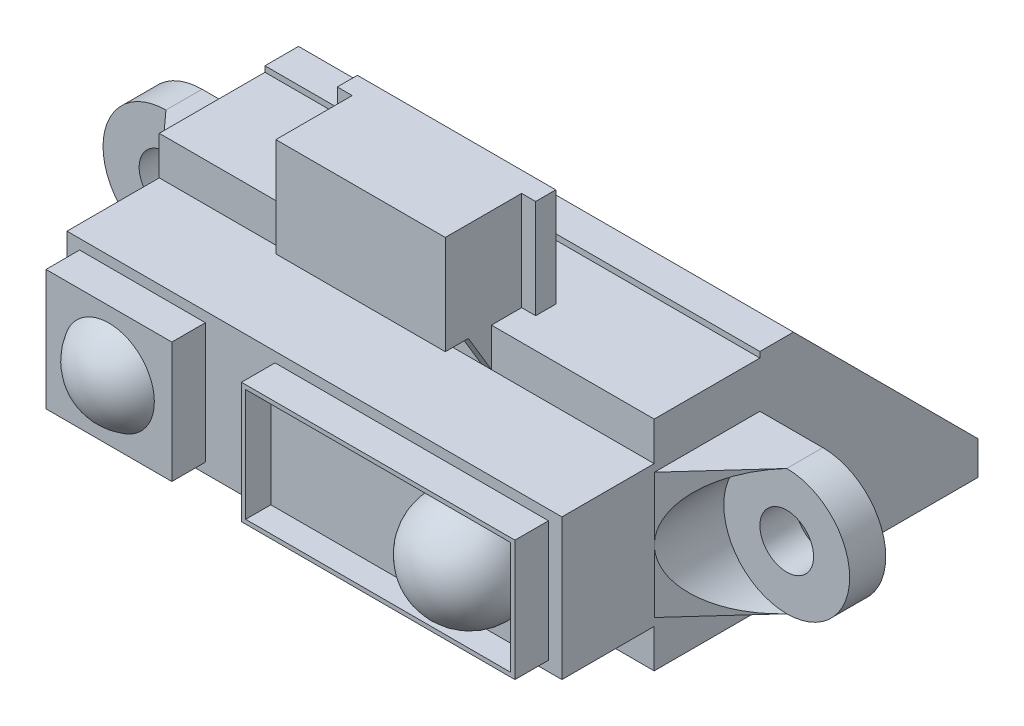
SolidWorks part; units mm, degrees
ref_plane "Plan de face" through (0, 0, 0) normal (0, 0, 1) x (1, 0, 0)
ref_plane "Plan de dessus" through (0, 0, 0) normal (0, 1, 0) x (1, 0, 0)
ref_plane "Plan de droite" through (0, 0, 0) normal (1, 0, 0) x (0, 0, -1)
sketch "Esquisse1" plane through (0, 0, 0) normal (0, 0, 1) x (1, 0, 0)
  line L1 (1.5656, 3.4963) -> (16.3156, 3.4963)
  line L3 (1.5656, -9.5037) -> (16.3156, -9.5037)
  line L4 (16.3156, 3.4963) -> (16.3156, -9.5037)
  line L7 (20.0656, -7.0914) -> (16.3156, -7.0914)
  line L8 (20.0656, 0.4086) -> (16.3156, 0.4086)
  line L9 (16.3156, 0.4086) -> (16.3156, -7.0914)
  line L10 (1.5656, 3.4963) -> (1.5656, -9.5037)
  arc A1 (20.0656, -7.0914) -> (20.0656, 0.4086) centre (20.0656, -3.3414) ccw
  circle A3 centre (20.0656, -3.3414) radius 1.6
  dimension "D5" = 7.5
  dimension "D6" = 3.2
  dimension "D1" = 14.75
  dimension "D2" = 13
extrude "Boss.-Extru.2" add sketch "Esquisse1" along normal blind 2.15 contours A1 L8 L9 L7
sketch "Esquisse2" plane through (0, 0, 0) normal (0, 0, 1) x (1, 0, 0)
  line L0 (16.3156, 0.4086) -> (16.3156, -7.0914) construction
  line L1 (1.5656, 3.1586) -> (16.3156, 3.1586)
  line L2 (1.5656, 3.1586) -> (1.5656, -9.8414)
  line L3 (1.5656, -9.8414) -> (16.3156, -9.8414)
  line L4 (16.3156, 3.1586) -> (16.3156, -9.8414)
  dimension "D3" = 0
  dimension "D1" = 14.75
  dimension "D2" = 13
  dimension "D4" = 2.75
extrude "Boss.-Extru.3" add sketch "Esquisse2" along normal blind 6.3 separate body
sketch "Esquisse8" plane through (16.3156, 0, 0) normal (1, 0, 0) x (0, 0, -1)
  line L0 (-2.1441, -7.0745) -> (-6.3, -7.0745)
  line L1 (-6.3, -9.8414) -> (-6.3, 3.1586) construction
  line L2 (-2.1441, 0.4088) -> (-6.3, 0.4088)
  line L3 (-6.3, -7.0745) -> (-6.3, 0.4088)
  line L4 (-2.1441, 0.4088) -> (-2.1441, -7.0745)
sketch "Esquisse9" plane through (0, 0, 2.15) normal (0, 0, 1) x (1, 0, 0)
  line L0 (20.0656, -7.0914) -> (16.3156, -7.0914) construction
  line L1 (16.3156, 0.4086) -> (19.8581, 0.4086)
  line L2 (16.3156, 0.4086) -> (16.3156, -7.0914)
  line L3 (16.3156, -7.0914) -> (19.8581, -7.0914)
  line L4 (19.8581, 0.4086) -> (19.8581, -7.0914)
sketch "Esquisse10" plane through (0, -7.0914, 0) normal (0, -1, 0) x (1, 0, 0)
  line L0 (16.3156, 6.2878) -> (20.0656, 2.15)
  line L1 (16.3156, 2.1441) -> (16.3156, 6.3) construction
  line L2 (20.0656, 2.15) -> (16.3156, 2.15)
  line L3 (16.3156, 2.15) -> (19.8581, 2.15) construction
  line L4 (16.3156, 2.15) -> (16.3156, 6.2878)
extrude "Boss.-Extru.4" add sketch "Esquisse10" against normal blind 7.5
extrude "Boss-Extrude1" add sketch "Esquisse1<5>" against normal blind 13 contours L1 L10 L3 L4 region at (8.9406, -3.0037, 0)
sketch "Esquisse1<5>" plane through (0, 0, 0) normal (0, 0, 1) x (1, 0, 0) same geometry as "Esquisse1"
chamfer "Chamfer1" distance 11 angle 45 1 edges at (8.9406, 3.4963, -13)
sketch "Esquisse3" plane through (0, 0, 0) normal (0, 0, 1) x (1, 0, 0)
  circle A2 centre (-16.9344, -3.3414) radius 1.6
  circle A3 centre (20.0656, -3.3414) radius 1.6
  dimension "D4" = 3.2
  dimension "D6" = 3.2
extrude "Enlèv. mat.-Extru.1" cut sketch "Esquisse3" along normal blind 6.3 contours A3 | A2
sketch "Esquisse11" plane through (0, 0, 6.3) normal (0, 0, 1) x (1, 0, 0)
  circle A0 centre (20.0656, -3.3414) radius 3.75
  arc A2 (20.0656, -7.0914) -> (20.0656, 0.4086) centre (20.0656, -3.3414) ccw construction
  dimension "D1" = 0
extrude "Enlèv. mat.-Extru.2" cut sketch "Esquisse11" against normal blind 4.15
sketch "Esquisse12" plane through (0, 0, 6.3) normal (0, 0, 1) x (1, 0, 0)
  line L0 (16.3156, -9.8414) -> (16.3156, 3.1586) construction
  line L1 (16.3156, -7.5414) -> (1.5656, -7.5414)
  line L2 (16.3156, -7.5414) -> (16.3156, 0.8586)
  line L3 (16.3156, 0.8586) -> (1.5656, 0.8586)
  line L4 (1.5656, -7.5414) -> (1.5656, 0.8586)
  line L5 (1.5656, 3.1586) -> (1.5656, -9.8414) construction
  dimension "D1" = 8.4
  dimension "D2" = 4.2
extrude "Boss.-Extru.5" add sketch "Esquisse12" along normal blind 5.5
mirror "Symétrie15" about plane through (1.5656, 3.1586, 6.3) normal (1, 0, 0) of bodies 109
sketch "Esquisse13" plane through (0, 0, 11.8) normal (0, 0, 1) x (1, 0, 0)
  line L0 (16.3156, -7.5414) -> (16.3156, 0.8586) construction
  line L1 (-0.7844, 0.2586) -> (15.5156, 0.2586)
  line L2 (-0.7844, 0.2586) -> (-0.7844, -6.9414)
  line L3 (-0.7844, -6.9414) -> (15.5156, -6.9414)
  line L4 (15.5156, 0.2586) -> (15.5156, -6.9414)
  line L5 (16.3156, 0.8586) -> (-13.1844, 0.8586) construction
  dimension "D1" = 0.8
  dimension "D2" = 16.3
  dimension "D3" = 0.6
  dimension "D4" = 7.2
extrude "Boss.-Extru.6" add sketch "Esquisse13" along normal blind 2
sketch "Esquisse14" plane through (0, 0, 11.8) normal (0, 0, 1) x (1, 0, 0)
  line L0 (-13.1844, -7.5414) -> (-13.1844, 0.8586) construction
  line L1 (-12.4344, 0.2586) -> (-4.9344, 0.2586)
  line L2 (-12.4344, 0.2586) -> (-12.4344, -6.9414)
  line L3 (-12.4344, -6.9414) -> (-4.9344, -6.9414)
  line L4 (-4.9344, 0.2586) -> (-4.9344, -6.9414)
  line L5 (16.3156, 0.8586) -> (-13.1844, 0.8586) construction
  dimension "D1" = 0.75
  dimension "D2" = 7.5
  dimension "D3" = 0.6
  dimension "D4" = 7.2
extrude "Boss.-Extru.7" add sketch "Esquisse14" along normal blind 2
sketch "Esquisse16" plane through (0, 0, 13.8) normal (0, 0, 1) x (1, 0, 0)
  line L1 (-0.5344, 0.0086) -> (15.2656, 0.0086)
  line L2 (-0.5344, 0.0086) -> (-0.5344, -6.6914)
  line L3 (-0.5344, -6.6914) -> (15.2656, -6.6914)
  line L4 (15.2656, 0.0086) -> (15.2656, -6.6914)
  line L5 (15.5156, 0.2586) -> (-0.7844, 0.2586) construction
  line L6 (-0.7844, 0.2586) -> (-0.7844, -6.9414) construction
  line L8 (-0.7844, -6.9414) -> (15.5156, -6.9414) construction
  line L9 (15.5156, -6.9414) -> (15.5156, 0.2586) construction
  dimension "D1" = 0.25
  dimension "D2" = 0.25
  dimension "D3" = 0.25
  dimension "D4" = 0.25
extrude "Enlèv. mat.-Extru.3" cut sketch "Esquisse16" against normal blind 1.5
sketch "Esquisse15" plane through (0, 0, 12.3) normal (0, 0, 1) x (1, 0, 0)
  line L0 (-12.4344, 0.2586) -> (-12.4344, -6.9414) construction
  line L1 (14.5375, -3.3414) -> (8.0938, -3.3414)
  line L2 (-11.7792, -3.3414) -> (-5.5896, -3.3414)
  line L3 (-0.7844, -6.9414) -> (15.5156, -6.9414) construction
  line L4 (-12.4344, -6.9414) -> (-4.9344, -6.9414) construction
  line L5 (7.2302, -3.3414) -> (14.8961, -3.3414) construction
  line L6 (-12.1304, -3.3414) -> (-5.3192, -3.3414) construction
  arc A0 (-11.7792, -3.3414) -> (-5.5896, -3.3414) centre (-8.6844, -3.3414) ccw
  arc A1 (8.0938, -3.3414) -> (14.5375, -3.3414) centre (11.3156, -3.3414) ccw
  dimension "D5" = 6.4438
  dimension "D1" = 3.75
  dimension "D2" = 20
  dimension "D3" = 3.6
  dimension "D4" = 3.6
revolve "Révolution14" add sketch "Esquisse15" angle 360 about L6
sketch "Esquisse18" plane through (0, 3.1586, 0) normal (0, 1, 0) x (1, 0, 0)
  line L2 (6.6156, -4.5) -> (6.6156, -9.05)
  line L3 (6.6156, -9.05) -> (-3.4844, -9.05)
  line L4 (-3.4844, -4.5) -> (-3.4844, -9.05)
  line L5 (1.5656, -3.3236) -> (1.5656, -6.9287) construction
  line L6 (-13.1844, -6.3) -> (-13.1844, 0) construction
  line L8 (-4.3735, -3.3) -> (7.451, -3.3)
  line L9 (-4.3735, -3.3) -> (-4.3735, -4.5)
  line L10 (-4.3735, -4.5) -> (-3.4844, -4.5)
  line L11 (7.451, -3.3) -> (7.451, -4.5)
  line L12 (16.3156, -11.8) -> (-13.1844, -11.8) construction
  line L13 (6.6156, -4.5) -> (7.451, -4.5)
  dimension "D2" = 2.75
  dimension "D3" = 10.1
  dimension "D4" = 14.75
  dimension "D5" = 5.05
  dimension "D6" = 1.2
extrude "Boss.-Extru.9" add sketch "Esquisse18" along normal blind 5.9
sketch "Esquisse19" plane through (-3.4844, 0, 0) normal (-1, 0, 0) x (0, 0, 1)
  line L0 (6.3, 0.8586) -> (7.675, 3.1586)
  line L1 (6.3, 3.1586) -> (9.05, 3.1586) construction
  line L2 (7.675, 3.1586) -> (6.3, 3.1586)
  line L3 (6.3, 3.1586) -> (6.3, 0.8586)
extrude "Boss.-Extru.10" add sketch "Esquisse19" against normal blind 10.1
sketch "Esquisse20" plane through (0, 0, 6.3) normal (0, 0, 1) x (1, 0, 0)
  line L0 (6.6156, 3.1586) -> (-3.4844, 3.1586) construction
  line L1 (-2.9584, 3.1586) -> (6.0088, 3.1586)
  line L2 (-2.9584, 3.1586) -> (-2.9584, 0.8586)
  line L3 (-2.9584, 0.8586) -> (6.0088, 0.8586)
  line L4 (6.0088, 3.1586) -> (6.0088, 0.8586)
  line L5 (16.3156, 0.8586) -> (-13.1844, 0.8586) construction
extrude "Enlèv. mat.-Extru.4" cut sketch "Esquisse20" along normal blind 10.1
